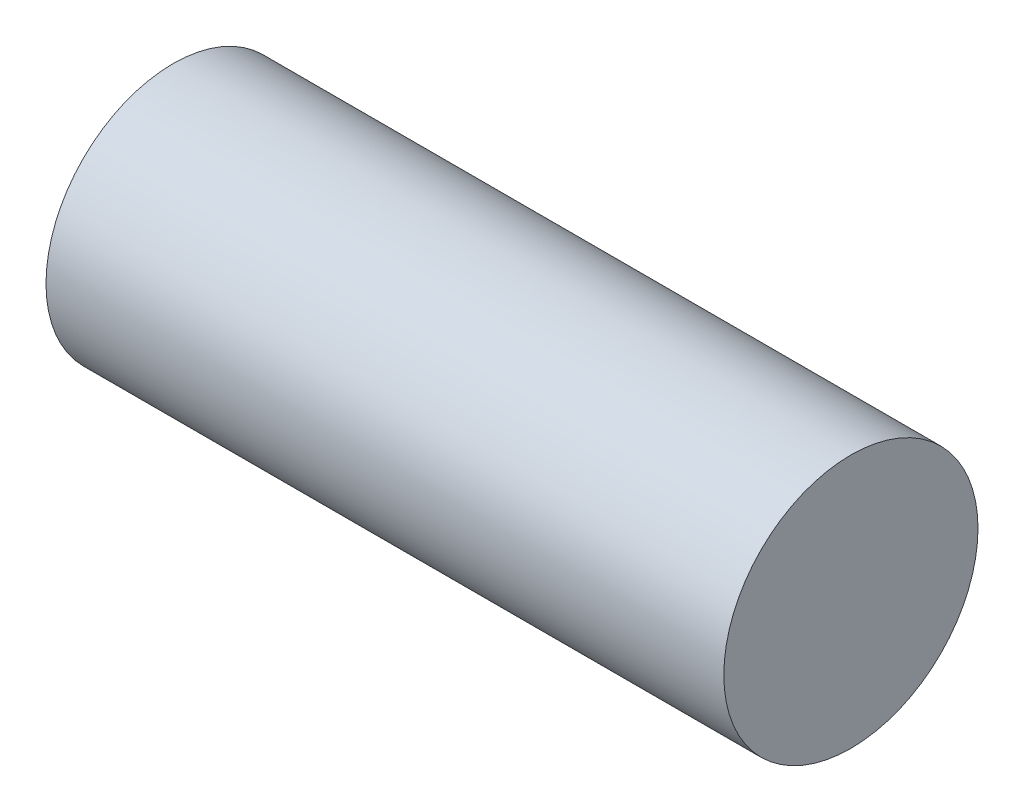
SolidWorks part; units mm, degrees
material "Chrome Stainless Steel"
ref_plane "Front Plane" through (0, 0, 0) normal (0, 0, 1) x (1, 0, 0)
ref_plane "Top Plane" through (0, 0, 0) normal (0, 1, 0) x (1, 0, 0)
ref_plane "Right Plane" through (0, 0, 0) normal (1, 0, 0) x (0, 0, -1)
other "Configuration Table"
sketch "Sketch1" plane through (0, 0, 0) normal (1, 0, 0) x (0, 0, -1)
  circle A0 centre (0, 0) radius 6
  dimension "D1" = 12
extrude "Boss-Extrude1" add sketch "Sketch1" along normal blind 32
ref_plane "Plane1" through (16, 0, 0) normal (1, 0, 0) x (0, 0, -1)
ref_axis "Axis1" through (32, 0, 0) along (-1, 0, 0)
